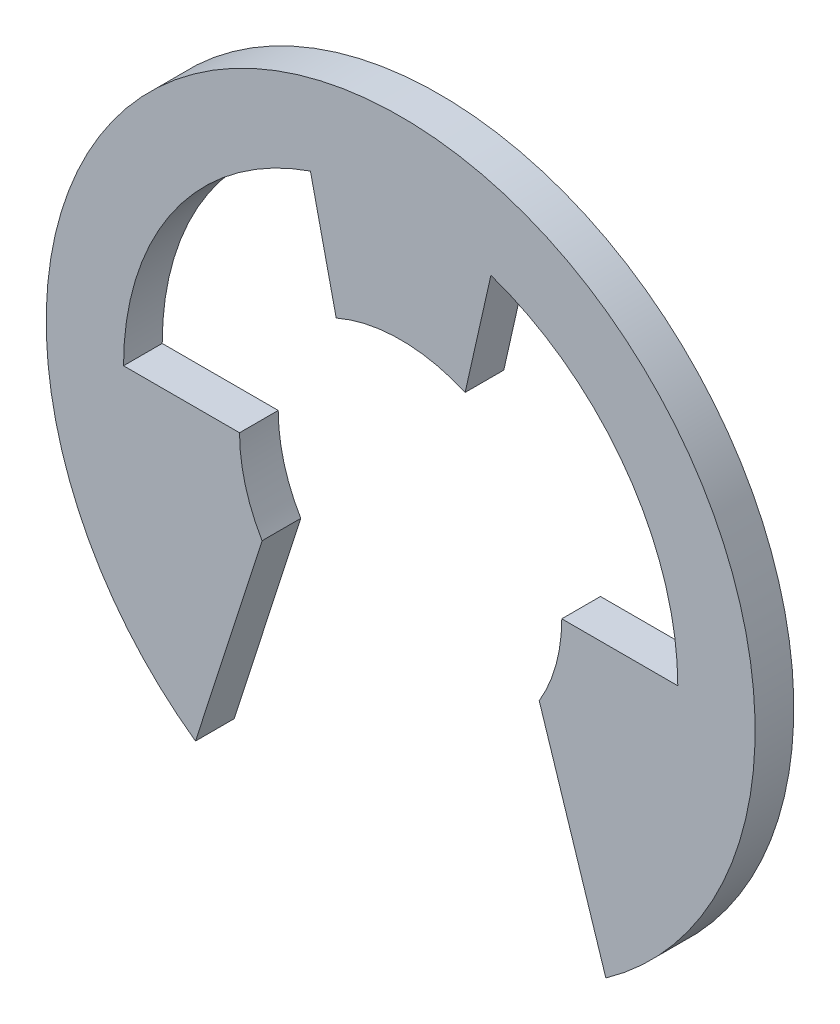
SolidWorks part; units mm, degrees
ref_plane "正面" through (0, 0, 0) normal (0, 0, 1) x (1, 0, 0)
ref_plane "平面" through (0, 0, 0) normal (0, 1, 0) x (1, 0, 0)
ref_plane "右側面" through (0, 0, 0) normal (1, 0, 0) x (0, 0, -1)
ref_plane "平面1" through (0, 0, 0) normal (0, 0, 1) x (1, 0, 0)
sketch "ｽｹｯﾁ1" plane through (0, 0, 0) normal (0, 0, 1) x (1, 0, 0)
  line L0 (-3.1835, -4.485) -> (-2.15, -1.2757)
  line L1 (-2.5, 0) -> (-4.3, 0)
  line L2 (-1.4, 4.0657) -> (-1.0001, 2.2912)
  line L3 (1.0001, 2.2912) -> (1.4, 4.0657)
  line L4 (4.3, 0) -> (2.5, 0)
  line L5 (2.15, -1.2757) -> (3.1835, -4.485)
  arc A0 (3.1835, -4.485) -> (-3.1835, -4.485) centre (0, 0) ccw
  arc A1 (-2.15, -1.2757) -> (-2.5, 0) centre (0, 0) cw
  arc A2 (-4.3, 0) -> (-1.4, 4.0657) centre (0, 0) cw
  arc A3 (-1.0001, 2.2912) -> (1.0001, 2.2912) centre (0, 0) cw
  arc A4 (1.4, 4.0657) -> (4.3, 0) centre (0, 0) cw
  arc A5 (2.5, 0) -> (2.15, -1.2757) centre (0, 0) cw
extrude "ﾎﾞｽ - 押し出し1" add sketch "ｽｹｯﾁ1" against normal blind 0.3 and the other way blind 0.3
